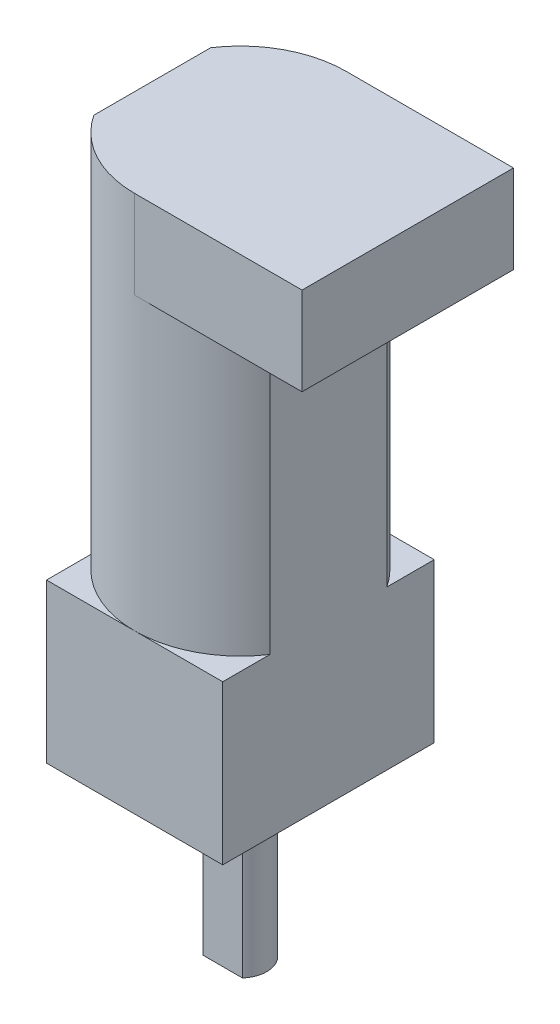
SolidWorks part; units mm, degrees
ref_plane "前视基准面" through (0, 0, 0) normal (0, 0, 1) x (1, 0, 0)
ref_plane "上视基准面" through (0, 0, 0) normal (0, 1, 0) x (1, 0, 0)
ref_plane "右视基准面" through (0, 0, 0) normal (1, 0, 0) x (0, 0, -1)
other "Configuration Table"
sketch "草图1" plane through (0, 0, 0) normal (0, 1, 0) x (1, 0, 0)
  line L0 (-5, -3.3166) -> (-5, 3.3166)
  line L1 (5, -3.3166) -> (5, 3.3166)
  line L2 (0, 6) -> (0, -6) construction
  arc A0 (-5, -3.3166) -> (5, -3.3166) centre (0, 0) ccw
  arc A1 (5, 3.3166) -> (-5, 3.3166) centre (0, 0) ccw
  dimension "D2" = 12
  dimension "D1" = 10
extrude "凸台-拉伸1" add sketch "草图1" along normal blind 21.5
sketch "草图2" plane through (0, 21.5, 0) normal (0, 1, 0) x (1, 0, 0)
  line L0 (-5, 3.3166) -> (-5, -3.3166) construction
  line L1 (0, 6) -> (9.5, 6)
  line L2 (0, 6) -> (0, -6)
  line L3 (0, -6) -> (9.5, -6)
  line L4 (9.5, 6) -> (9.5, -6)
  line L5 (0, 6) -> (9.5, -6) construction
  line L6 (0, -6) -> (9.5, 6) construction
  arc A0 (5, 3.3166) -> (-5, 3.3166) centre (0, 0) ccw construction
  arc A1 (-5, -3.3166) -> (5, -3.3166) centre (0, 0) ccw construction
  point P4 (4.75, 0)
  point P8 (0, -6)
  dimension "D1" = 14.5
extrude "凸台-拉伸2" add sketch "草图2" against normal blind 5
sketch "草图3" plane through (0, 0, 0) normal (0, -1, 0) x (1, 0, 0)
  line L0 (5, 3.3166) -> (5, -3.3166) construction
  line L1 (-5, -6) -> (5, -6)
  line L2 (-5, -6) -> (-5, 6)
  line L3 (-5, 6) -> (5, 6)
  line L4 (5, -6) -> (5, 6)
  line L5 (-5, -6) -> (5, 6) construction
  line L6 (-5, 6) -> (5, -6) construction
  line L7 (-5, -3.3166) -> (-5, 3.3166) construction
  arc A0 (5, 3.3166) -> (-5, 3.3166) centre (0, 0) ccw construction
  point P4 (0, 0)
  point P9 (0, 0)
extrude "凸台-拉伸3" add sketch "草图3" along normal blind 9
sketch "草图4" plane through (0, -9, 0) normal (0, -1, 0) x (1, 0, 0)
  circle A0 centre (0, 0) radius 2
  dimension "D1" = 4
extrude "凸台-拉伸4" add sketch "草图4" along normal blind 0.7
sketch "草图5" plane through (0, -9.7, 0) normal (0, -1, 0) x (1, 0, 0)
  line L0 (-1.118, 1) -> (1.118, 1)
  arc A0 (-1.118, 1) -> (1.118, 1) centre (0, 0) ccw
  dimension "D2" = 3
  dimension "D1" = 1
extrude "凸台-拉伸6" add sketch "草图5" along normal offset from surface (9.3 mm away) 10 up to face at (0, -9, -2) offset beyond the face yes
